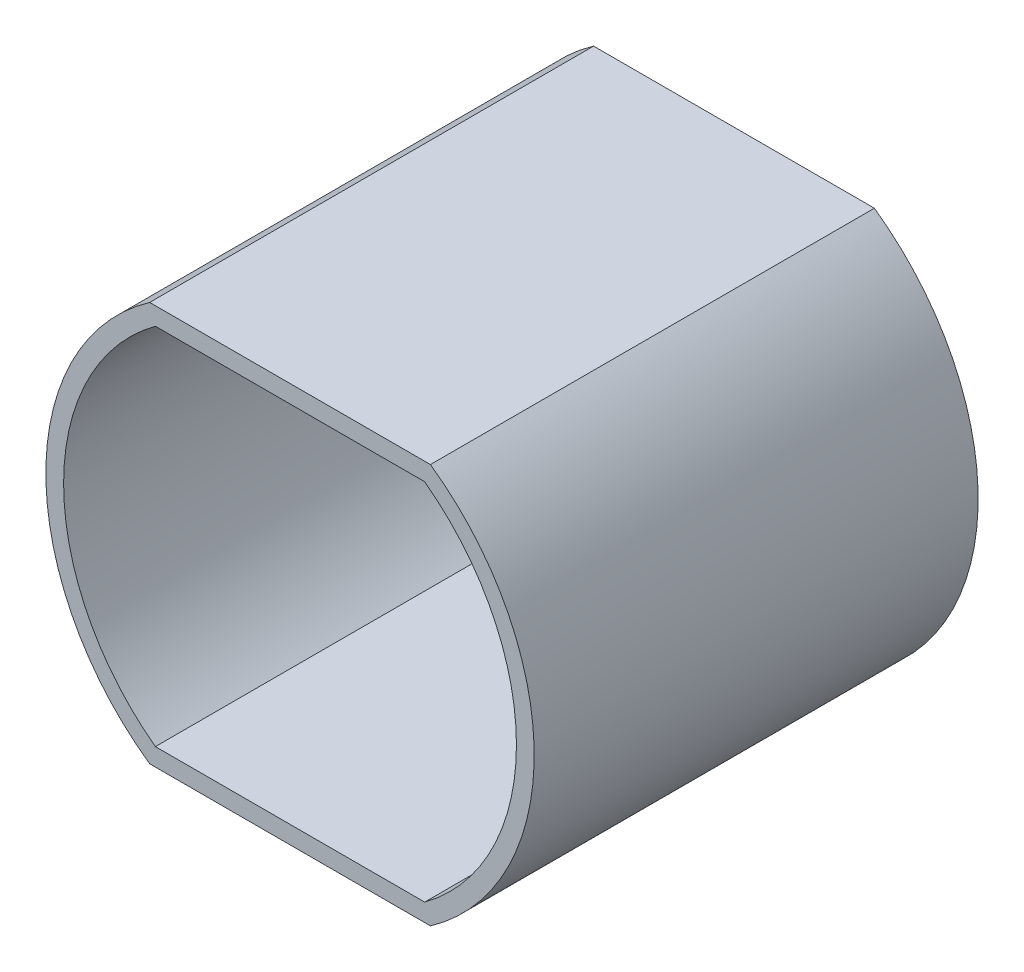
SolidWorks part; units mm, degrees
ref_plane "Front Plane" through (0, 0, 0) normal (0, 0, 1) x (1, 0, 0)
ref_plane "Top Plane" through (0, 0, 0) normal (0, 1, 0) x (1, 0, 0)
ref_plane "Right Plane" through (0, 0, 0) normal (1, 0, 0) x (0, 0, -1)
sketch "Sketch2" plane through (0, 0, 0) normal (0, 0, 1) x (1, 0, 0)
  line L3 (15.8114, 22.5) -> (-15.8114, 22.5)
  line L5 (15.8114, -22.5) -> (-15.8114, -22.5)
  arc A1 (15.8114, -22.5) -> (15.8114, 22.5) centre (0, 0) ccw
  arc A2 (-15.8114, 22.5) -> (-15.8114, -22.5) centre (0, 0) ccw
  circle A3 centre (0, 0) radius 4.75
extrude "Boss-Extrude8" add sketch "Sketch2" along normal blind 50
shell "Shell4" thickness 2 removed face at (4.75, 0, 50) removed face at (0, 0, 50)
